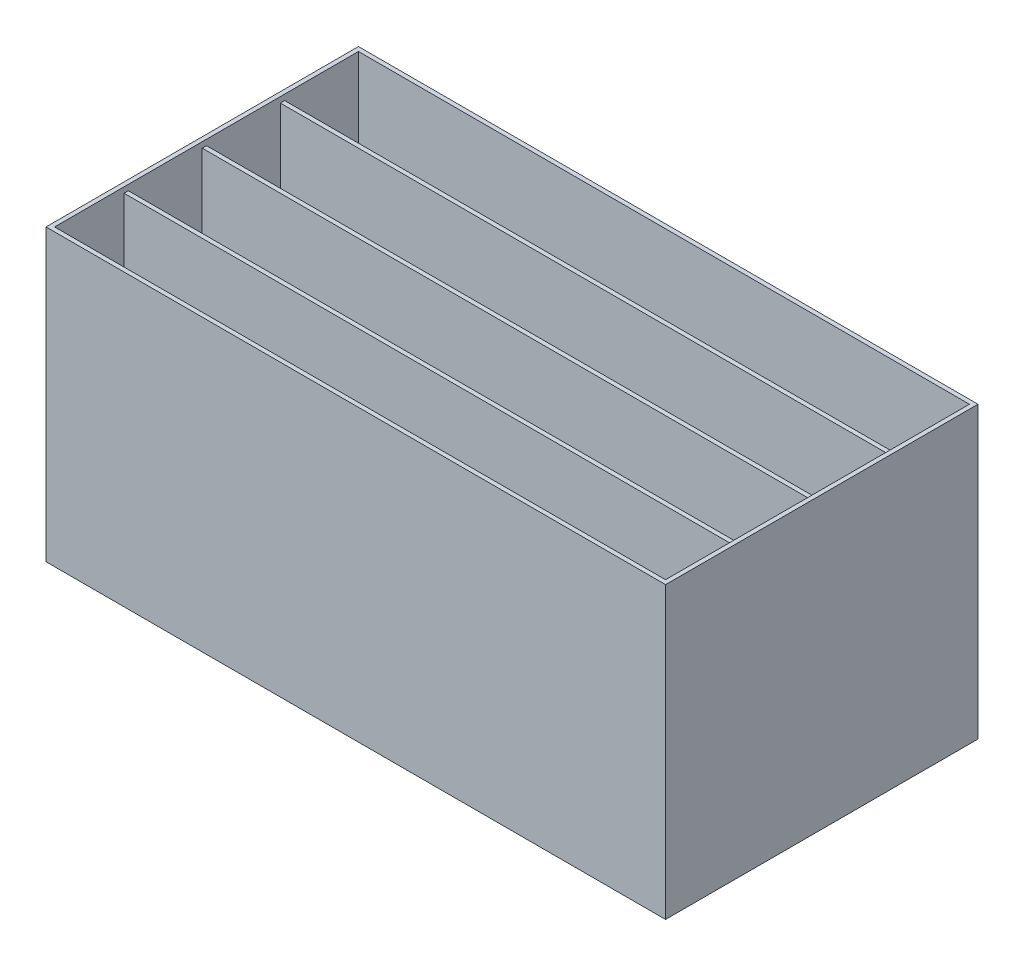
SolidWorks part; units mm, degrees
material "Glass"
ref_plane "Front Plane" through (0, 0, 0) normal (0, 0, 1) x (1, 0, 0)
ref_plane "Top Plane" through (0, 0, 0) normal (0, 1, 0) x (1, 0, 0)
ref_plane "Right Plane" through (0, 0, 0) normal (1, 0, 0) x (0, 0, -1)
ref_plane "Plane1" through (0, 391.414, 0) normal (0, 1, 0) x (1, 0, 0)
sketch "Sketch1" plane through (0, 0, 0) normal (0, 1, 0) x (1, 0, 0)
  line L1 (0, 0) -> (919.1625, 0)
  line L2 (0, 0) -> (0, 463.55)
  line L3 (0, 463.55) -> (919.1625, 463.55)
  line L4 (919.1625, 0) -> (919.1625, 463.55)
  dimension "D1" = 919.1625
  dimension "D2" = 463.55
extrude "Boss-Extrude1" add sketch "Sketch1" along normal blind 430.2125
shell "Shell1" thickness 6.35 removed face at (459.5813, 430.2125, -231.775)
sketch "Sketch2" plane through (0, 391.414, 0) normal (0, 1, 0) x (1, 0, 0)
  line L0 (6.35, 457.2) -> (6.35, 6.35) construction
  line L1 (6.35, 347.6625) -> (912.8125, 347.6625)
  line L2 (6.35, 347.6625) -> (6.35, 341.3125)
  line L3 (6.35, 341.3125) -> (912.8125, 341.3125)
  line L4 (912.8125, 347.6625) -> (912.8125, 341.3125)
  line L5 (912.8125, 6.35) -> (912.8125, 457.2) construction
  line L6 (6.35, 344.4875) -> (-41.0429, 344.4875) construction
  line L7 (912.8125, 457.2) -> (6.35, 457.2) construction
  line L8 (6.35, 231.775) -> (6.35, 225.425)
  line L9 (6.35, 231.775) -> (912.8125, 231.775)
  line L10 (912.8125, 231.775) -> (912.8125, 225.425)
  line L11 (6.35, 225.425) -> (912.8125, 225.425)
  line L12 (6.35, 115.8875) -> (6.35, 109.5375)
  line L13 (6.35, 115.8875) -> (912.8125, 115.8875)
  line L14 (912.8125, 115.8875) -> (912.8125, 109.5375)
  line L15 (6.35, 109.5375) -> (912.8125, 109.5375)
  line L16 (6.35, 228.6) -> (-36.5036, 228.6) construction
  line L18 (6.35, 112.7125) -> (-55.5434, 112.7125) construction
  dimension "D1" = 6.35
  dimension "D2" = 112.7125
  dimension "D4" = 115.8875
  dimension "D3" = 3
extrude "Boss-Extrude2" add sketch "Sketch2" against normal up to next and the other way blind 30.48
sketch "Sketch4" plane through (0, 430.2125, 0) normal (0, 1, 0) x (1, 0, 0)
  line L0 (6.35, 402.4312) -> (175.3542, 402.4312) construction
  line L1 (6.35, 457.2) -> (6.35, 347.6625) construction
  line L3 (6.35, 286.5437) -> (182.0227, 286.5437) construction
  line L4 (6.35, 341.3125) -> (6.35, 231.775) construction
  line L5 (6.35, 170.6562) -> (182.0227, 170.6562) construction
  line L6 (6.35, 225.425) -> (6.35, 115.8875) construction
  line L7 (6.35, 57.9438) -> (182.0227, 57.9438) construction
  line L8 (6.35, 109.5375) -> (6.35, 6.35) construction
